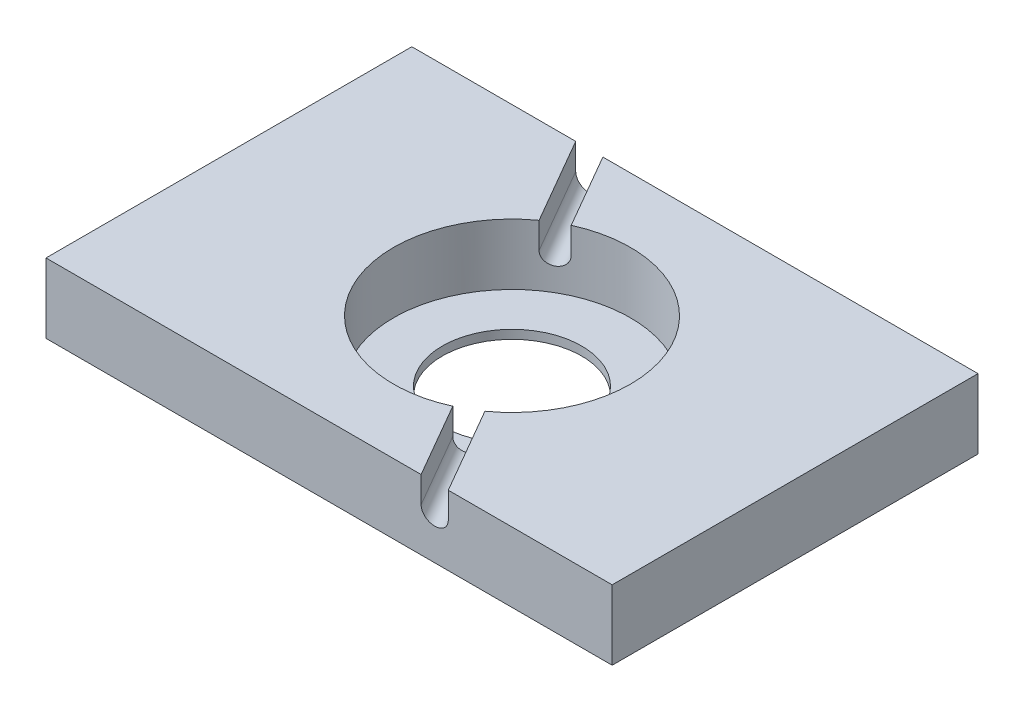
SolidWorks part; units mm, degrees
ref_plane "Piano frontale" through (0, 0, 0) normal (0, 0, 1) x (1, 0, 0)
ref_plane "Piano superiore" through (0, 0, 0) normal (0, 1, 0) x (1, 0, 0)
ref_plane "Piano destro" through (0, 0, 0) normal (1, 0, 0) x (0, 0, -1)
sketch "Schizzo1" plane through (0, 0, 0) normal (0, 1, 0) x (1, 0, 0)
  circle A0 centre (0, 0) radius 27
  dimension "D1" = 54
extrude "Estrusione-Estrusione1" add sketch "Schizzo1" along normal blind 1
sketch "Schizzo2" plane through (0, 1, 0) normal (0, 1, 0) x (1, 0, 0)
  circle A0 centre (0, 0) radius 8
extrude "Taglio-Estrusione1" cut sketch "Schizzo2" against normal through all
sketch "Schizzo3" plane through (0, 1, 0) normal (0, 1, 0) x (1, 0, 0)
  circle A0 centre (0, 0) radius 13.6
  circle A1 centre (0, 0) radius 27
  dimension "D1" = 54
extrude "Estrusione-Estrusione2" add sketch "Schizzo3" along normal blind 5
sketch "Schizzo5" plane through (0, 6, 0) normal (0, 1, 0) x (1, 0, 0)
  line L1 (32.5, -21) -> (-32.5, -21)
  line L2 (32.5, -21) -> (32.5, 21)
  line L3 (32.5, 21) -> (-32.5, 21)
  line L4 (-32.5, -21) -> (-32.5, 21)
  line L5 (32.5, -21) -> (-32.5, 21) construction
  line L6 (32.5, 21) -> (-32.5, -21) construction
  circle A0 centre (0, 0) radius 13.6
  dimension "D1" = 42
  dimension "D2" = 65
extrude "Estrusione-Estrusione3" add sketch "Schizzo5" along normal blind 2 and the other way blind 1
sketch "Schizzo6" plane through (0, 6, 0) normal (0, -1, 0) x (-1, 0, 0)
  line L0 (0, 0) -> (0, 7.5) construction
  line L1 (0, 7.5) -> (22.998, 7.5) construction
  line L2 (0, 0) -> (0, -7.5) construction
  line L3 (0, -7.5) -> (-22.998, -7.5) construction
  line L4 (0, 0) -> (6.8, 11.7779) construction
  line L5 (6.8, 11.7779) -> (-6.8, -11.7779) construction
  line L6 (0, 0) -> (-11.7779, 6.8) construction
  line L7 (-11.7779, 6.8) -> (11.7779, -6.8) construction
  circle A0 centre (0, 0) radius 24.19
  circle A1 centre (0, 0) radius 13.6 construction
  circle A2 centre (0, 0) radius 13.6 construction
  dimension "D1" = 48.38
  dimension "D2" = 7.5
  dimension "D3" = 7.5
  dimension "D4" = 30
  dimension "D5" = 90
sketch3d "Schizzo3D1"
  line L0 (0, 6, 0) -> (11.7779, 6, -6.8) construction
  line L1 (0, 6, 0) -> (-6.8, 6, -11.7779) construction
  line L2 (0, 6, 0) -> (0, 5, 0) construction
  line L3 (11.7779, 6, -6.8) -> (-11.7779, 6, 6.8) construction
  circle A0 centre (0, 5, 0) radius 1.35
  point P9 (0.675, 5, 1.1691)
  dimension "D2" = 2.7
  dimension "D1" = 1
extrude "Taglio-Estrusione2" cut sketch "Schizzo3D1" along direction (-0.5, 0, -0.866) on the side against the normal through all and the other way through all
sketch3d "Schizzo3D2"
  line L0 (0, 6, 0) -> (11.7779, 6, -6.8) construction
  line L1 (0, 6, 0) -> (-6.8, 6, -11.7779) construction
  line L2 (11.7779, 6, -6.8) -> (-11.7779, 6, 6.8) construction
  line L3 (1.1691, 5, -0.675) -> (-1.1691, 5, 0.675)
  line L4 (-1.1691, 5, 0.675) -> (-1.1691, 10, 0.675)
  line L5 (1.1691, 5, -0.675) -> (1.1691, 10, -0.675)
  line L6 (-1.1691, 10, 0.675) -> (1.1691, 10, -0.675)
  point P4 (0, 6, 0)
  dimension "D1" = 2.7
  dimension "D3" = 5
  dimension "D2" = 5
extrude "Taglio-Estrusione3" cut sketch "Schizzo3D2" along direction (0.5, 0, 0.866) on the side against the normal through all and the other way through all
sketch "Schizzo8" plane through (0, 6, 0) normal (0, 1, 0) x (1, 0, 0)
  line L1 (32.5, -21) -> (-32.5, -21)
  line L2 (32.5, -21) -> (32.5, 21)
  line L3 (32.5, 21) -> (-32.5, 21)
  line L4 (-32.5, -21) -> (-32.5, 21)
  line L5 (32.5, -21) -> (-32.5, 21) construction
  line L6 (32.5, 21) -> (-32.5, -21) construction
  line L7 (40.7304, -29.5052) -> (-40.7304, -29.5052)
  line L8 (40.7304, -29.5052) -> (40.7304, 29.5052)
  line L9 (40.7304, 29.5052) -> (-40.7304, 29.5052)
  line L10 (-40.7304, -29.5052) -> (-40.7304, 29.5052)
  line L11 (40.7304, -29.5052) -> (-40.7304, 29.5052) construction
  line L12 (40.7304, 29.5052) -> (-40.7304, -29.5052) construction
  point P0 (0, 0)
  point P6 (0, 0)
  dimension "D1" = 42
  dimension "D2" = 65
extrude "Taglio-Estrusione5" cut sketch "Schizzo8" against normal through all
sketch "Schizzo10" plane through (0, 5, 0) normal (0, -1, 0) x (1, 0, 0)
  line L1 (-32.5, -21) -> (-16.9706, -21)
  line L2 (-32.5, -21) -> (-32.5, 21)
  line L3 (-32.5, 21) -> (-16.9706, 21)
  line L4 (-16.9706, -21) -> (-16.9706, 21)
extrude "Estrusione-Estrusione4" add sketch "Schizzo10" along normal blind 5
sketch "Schizzo11" plane through (0, 5, 0) normal (0, -1, 0) x (1, 0, 0)
  line L1 (32.5, -21) -> (16.9706, -21)
  line L2 (32.5, -21) -> (32.5, 21)
  line L3 (32.5, 21) -> (16.9706, 21)
  line L4 (16.9706, -21) -> (16.9706, 21)
extrude "Estrusione-Estrusione5" add sketch "Schizzo11" along normal blind 5
